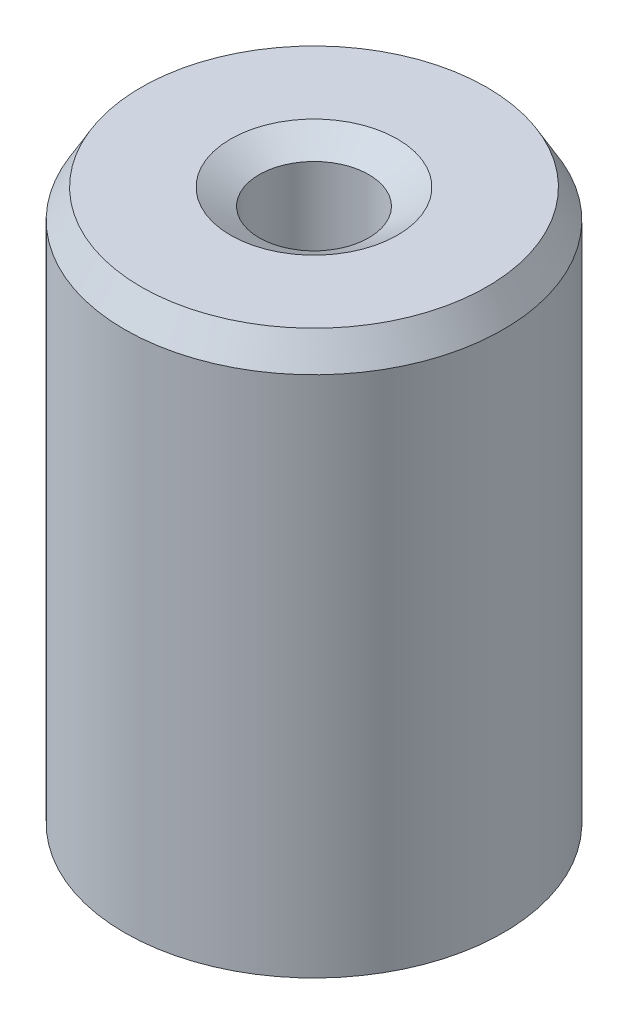
SolidWorks part; units mm, degrees
ref_plane "Front Plane" through (0, 0, 0) normal (0, 0, 1) x (1, 0, 0)
ref_plane "Top Plane" through (0, 0, 0) normal (0, 1, 0) x (1, 0, 0)
ref_plane "Right Plane" through (0, 0, 0) normal (1, 0, 0) x (0, 0, -1)
sketch "Sketch1" plane through (0, 0, 0) normal (0, 1, 0) x (1, 0, 0)
  circle A0 centre (0, 0) radius 5
  dimension "SLEEVE_OD" = 10
extrude "Boss-Extrude1" add sketch "Sketch1" along normal blind 14.9839
sketch "Sketch2" plane through (0, 0, 0) normal (0, 1, 0) x (1, 0, 0)
  circle A0 centre (0, 0) radius 1.4464
  dimension "BORE_D" = 2.8927
extrude "Cut-Extrude1" cut sketch "Sketch2" along normal through all
chamfer "Chamfer1" distance 0.7556 angle 30 4 edges at (0, 14.9839, 1.4464) (0, 0, 1.4464) (0, 0, 5) (0, 14.9839, 5) first distance on face at (0, 14.9839, 1.4464) first distance on face at (0, 0, 1.4464) first distance on face at (0, 14.9839, 5)
